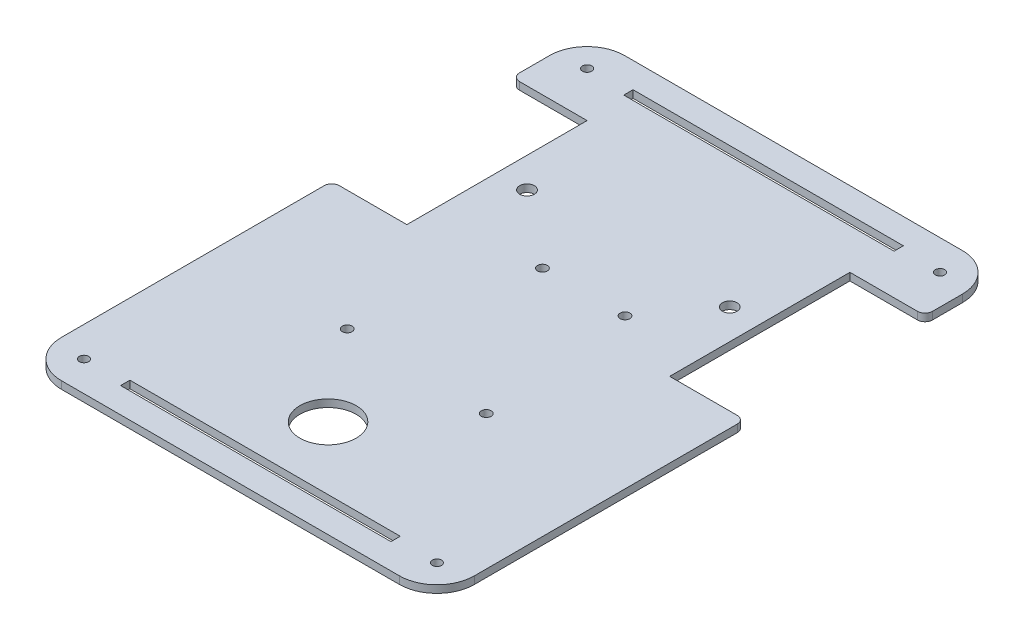
SolidWorks part; units mm, degrees
material "ABS"
ref_plane "Front Plane" through (0, 0, 0) normal (0, 0, 1) x (1, 0, 0)
ref_plane "Top Plane" through (0, 0, 0) normal (0, 1, 0) x (1, 0, 0)
ref_plane "Right Plane" through (0, 0, 0) normal (1, 0, 0) x (0, 0, -1)
sketch "Sketch2" plane through (0, 0, 0) normal (0, 1, 0) x (1, 0, 0)
  line L0 (-148.7583, 0) -> (98.0966, 0) construction
  line L1 (-69.85, -95.25) -> (69.85, -95.25)
  line L2 (-69.85, -95.25) -> (-69.85, 95.25)
  line L3 (-69.85, 95.25) -> (69.85, 95.25)
  line L4 (69.85, -95.25) -> (69.85, 95.25)
  line L5 (-69.85, -95.25) -> (69.85, 95.25) construction
  line L6 (-69.85, 95.25) -> (69.85, -95.25) construction
  line L7 (0, 121.1686) -> (0, -125.6862) construction
  point P0 (0, 0)
  dimension "D1" = 190.5
  dimension "D2" = 139.7
extrude "Base Plate" add sketch "Sketch2" along normal blind 2.54
sketch "Sketch4" plane through (0, 2.54, 0) normal (0, 1, 0) x (1, 0, 0)
  line L0 (0, -95.25) -> (0, 95.25) construction
  line L1 (-69.85, -95.25) -> (69.85, -95.25) construction
  line L2 (69.85, 95.25) -> (-69.85, 95.25) construction
  line L3 (-34.66, -69.85) -> (-34.66, -40.894) construction
  line L4 (-34.66, -40.894) -> (-58.79, -40.894) construction
  line L5 (-58.79, -40.894) -> (-58.79, -69.85) construction
  line L6 (-58.79, -69.85) -> (-34.66, -69.85) construction
  line L7 (69.85, -95.25) -> (69.85, 95.25) construction
  line L8 (-69.85, 95.25) -> (-69.85, -95.25) construction
  circle A0 centre (-58.79, -69.85) radius 1.8415
  circle A1 centre (-34.66, -69.85) radius 1.8415
  circle A2 centre (-34.66, -40.894) radius 1.8415
  circle A3 centre (-58.79, -40.894) radius 1.8415
  circle A4 centre (34.66, -69.85) radius 1.8415
  circle A5 centre (58.79, -69.85) radius 1.8415
  circle A6 centre (58.79, -40.894) radius 1.8415
  circle A7 centre (34.66, -40.894) radius 1.8415
  point P0 (-58.79, -69.85)
  point P1 (-58.79, -40.894)
  point P2 (-34.66, -40.894)
  point P3 (-34.66, -69.85)
  dimension "D4" = 3.683
  dimension "D1" = 28.956
  dimension "D2" = 24.13
  dimension "D3" = 11.06
  dimension "D5" = 25.4
sketch "Sketch5" plane through (0, 2.54, 0) normal (0, 1, 0) x (1, 0, 0)
  line L0 (-69.85, 8.89) -> (-44.45, 8.89)
  line L1 (-69.85, 95.25) -> (-69.85, -95.25) construction
  line L2 (-44.45, 8.89) -> (-44.45, 69.85)
  line L3 (-44.45, 69.85) -> (-69.85, 69.85)
  line L4 (-69.85, 69.85) -> (-69.85, 8.89)
  line L5 (-69.85, -95.25) -> (69.85, -95.25) construction
  line L6 (69.85, 95.25) -> (-69.85, 95.25) construction
  line L7 (0, -95.25) -> (0, 95.25) construction
  line L9 (44.45, 69.85) -> (69.85, 69.85)
  line L10 (44.45, 8.89) -> (44.45, 69.85)
  line L11 (69.85, 8.89) -> (44.45, 8.89)
  line L12 (69.85, 69.85) -> (69.85, 8.89)
  dimension "D1" = 25.4
  dimension "D2" = 60.96
  dimension "D3" = 25.4
extrude "Steering Wheels Holes" cut sketch "Sketch5" against normal blind 6.35
fillet "Fillet1" radius 12.7 4 edges at (69.85, 1.27, -95.25) (-69.85, 1.27, -95.25) (69.85, 1.27, 95.25) (-69.85, 1.27, 95.25)
fillet "Fillet2" radius 2.54 4 edges at (69.85, 1.27, -69.85) (69.85, 1.27, -8.89) (-69.85, 1.27, -8.89) (-69.85, 1.27, -69.85)
sketch "Sketch6" plane through (0, 2.54, 0) normal (0, 1, 0) x (1, 0, 0)
  line L0 (-69.85, -95.25) -> (-69.85, 95.25) construction
  line L1 (-69.85, -95.25) -> (69.85, -95.25) construction
  line L2 (0, -88.935) -> (0, 95.5267) construction
  line L3 (-69.85, 6.35) -> (69.85, 6.35) construction
  point P0 (-59.69, -85.09)
  point P12 (-59.69, 97.79)
  point P13 (59.69, -85.09)
  point P14 (59.69, 97.79)
  point P15 (0, 0)
  dimension "D1" = 10.16
  dimension "D2" = 10.16
sketch "Sketch15" plane through (0, 2.54, 0) normal (0, 1, 0) x (1, 0, 0)
  line L0 (-69.85, -95.25) -> (-69.85, 95.25) construction
  line L1 (-69.85, 95.25) -> (69.85, 95.25) construction
  line L2 (0, 95.25) -> (0, 49.0943) construction
  line L3 (0, 121.1686) -> (0, -125.6862) construction
  point P0 (-59.69, 85.09)
  point P5 (59.69, 85.09)
  dimension "D1" = 10.16
  dimension "D2" = 10.16
sketch "Sketch18" plane through (0, 2.54, 0) normal (0, 1, 0) x (1, 0, 0)
  line L0 (0, 95.25) -> (0, -95.25) construction
  line L1 (57.15, 95.25) -> (-57.15, 95.25) construction
  line L2 (-57.15, -95.25) -> (57.15, -95.25) construction
  line L3 (-24.003, -31.75) -> (78.9561, -31.75) construction
  circle A0 centre (-8.763, 19.05) radius 1.651
  circle A1 centre (19.177, 19.05) radius 1.651
  circle A2 centre (-24.003, -31.75) radius 1.651
  circle A3 centre (24.3097, -33.02) radius 1.651
  point P6 (-8.763, 19.05)
  point P7 (19.177, 19.05)
  point P8 (-24.003, -31.75)
  point P9 (24.257, -26.67)
  dimension "D7" = 3.302
  dimension "D1" = 52.07
  dimension "D2" = 1.27
  dimension "D3" = 5.08
  dimension "D4" = 27.94
  dimension "D5" = 15.24
  dimension "D6" = 50.8
  dimension "D8" = 76.2
extrude "Holes for Arduino UNO" cut sketch "Sketch18" against normal through all
sketch "Sketch20" plane through (0, 2.54, 0) normal (0, 1, 0) x (1, 0, 0)
  line L0 (0, 95.25) -> (0, -95.25) construction
  line L1 (57.15, 95.25) -> (-57.15, 95.25) construction
  line L2 (-57.15, -95.25) -> (57.15, -95.25) construction
  circle A0 centre (0, -62.23) radius 9.525
  dimension "D1" = 19.05
  dimension "D2" = 33.02
extrude "Cutout for motor wires" cut sketch "Sketch20" against normal through all
sketch "Sketch21" plane through (0, 2.54, 0) normal (0, 1, 0) x (1, 0, 0)
  line L0 (-44.45, 39.37) -> (44.45, 39.37) construction
  line L1 (-44.45, 8.89) -> (-44.45, 69.85) construction
  line L2 (44.45, 69.85) -> (44.45, 8.89) construction
  line L3 (0, 95.25) -> (0, -21.3651) construction
  line L4 (57.15, 95.25) -> (-57.15, 95.25) construction
  point P6 (-34.29, 39.37)
  point P12 (34.29, 39.37)
  dimension "D1" = 10.16
hole_wizard "holes for steering " positions "Sketch22" profile "Sketch23" tap size "M6x1.0" standard "ANSI Metric" end condition through all
sketch "Sketch22" plane through (0, 2.54, 0) normal (0, 1, 0) x (1, 0, 0)
  point P0 (-34.29, 39.37)
  point P3 (34.29, 39.37)
sketch "Sketch23" plane through (-34.29, 2.54, -39.37) normal (1, 0, 0) x (0, 0, 1)
  line L0 (0, 0) -> (0, 2.54)
  line L1 (0, 2.54) -> (2.5, 2.54)
  line L2 (2.5, 2.54) -> (2.5, 0)
  line L5 (2.5, 0) -> (0, 0)
  line L11 (0, -6.35) -> (0, 107.95) construction
  dimension "Thru Tap Drill Dia." = 5
  dimension "Thru Tap Drill Depth" = 2.54
cosmetic thread "Hole Thread11" parameters "D2"=6
cosmetic thread "Hole Thread12" parameters "D2"=6
sketch "Sketch24" plane through (0, 2.54, 0) normal (0, 1, 0) x (1, 0, 0)
  line L0 (0, -95.25) -> (0, 95.25) construction
  line L1 (-57.15, -95.25) -> (57.15, -95.25) construction
  line L2 (57.15, 95.25) -> (-57.15, 95.25) construction
  line L3 (-69.85, 82.55) -> (-69.85, 72.39) construction
  circle A0 centre (-59.69, 85.09) radius 1.57
  circle A1 centre (-59.69, 85.09) radius 2.84
  dimension "D1" = 3.14
  dimension "D2" = 10.16
  dimension "D3" = 10.16
  dimension "D4" = 1.27
extrude "Cut-Extrude1" cut sketch "Sketch24" against normal blind 2.54 contours A0 region at (-59.69, 2.54, -85.09)
mirror "Mirror1" about plane through (0, 0, 0) normal (1, 0, 0) of "Cut-Extrude1"
sketch "Sketch25" plane through (0, 2.54, 0) normal (0, 1, 0) x (1, 0, 0)
  line L0 (0, -95.25) -> (0, 95.25) construction
  line L1 (-57.15, -95.25) -> (57.15, -95.25) construction
  line L2 (57.15, 95.25) -> (-57.15, 95.25) construction
  line L3 (-69.85, 6.35) -> (-69.85, -82.55) construction
  circle A0 centre (-59.69, -85.09) radius 1.57
  circle A2 centre (59.69, -85.09) radius 1.57
  dimension "D1" = 3.14
  dimension "D4" = 3.14
  dimension "D2" = 10.16
  dimension "D3" = 10.16
extrude "Cut-Extrude3" cut sketch "Sketch25" against normal blind 2.54
sketch "Sketch27" plane through (0, 2.54, 0) normal (0, 1, 0) x (1, 0, 0)
  line L12 (0, -95.25) -> (0, 166.7066) construction
  line L13 (-57.15, -95.25) -> (57.15, -95.25) construction
  line L14 (-59.69, -87.93) -> (59.69, -87.93) construction
  line L15 (59.69, -82.25) -> (-59.69, -82.25) construction
  line L16 (-45.72, -86.66) -> (45.72, -86.66)
  line L17 (-46.99, -87.93) -> (46.99, -87.93)
  line L18 (-46.99, -87.93) -> (-46.99, -82.25)
  line L19 (-46.99, -82.25) -> (46.99, -82.25)
  line L20 (46.99, -87.93) -> (46.99, -82.25)
  line L21 (45.72, -86.66) -> (45.72, -83.52)
  line L22 (-45.72, -83.52) -> (45.72, -83.52)
  line L23 (-45.72, -86.66) -> (-45.72, -83.52)
  line L24 (-59.69, 82.25) -> (59.69, 82.25) construction
  line L25 (59.69, 87.93) -> (-59.69, 87.93) construction
  line L26 (-45.72, 86.66) -> (45.72, 86.66)
  line L27 (-46.99, 82.25) -> (46.99, 82.25)
  line L28 (-46.99, 82.25) -> (-46.99, 87.93)
  line L29 (-46.99, 87.93) -> (46.99, 87.93)
  line L30 (46.99, 82.25) -> (46.99, 87.93)
  line L31 (45.72, 83.52) -> (45.72, 86.66)
  line L32 (-45.72, 83.52) -> (45.72, 83.52)
  line L33 (-45.72, 83.52) -> (-45.72, 86.66)
  circle A8 centre (-59.69, -85.09) radius 2.84
  circle A9 centre (-59.69, -85.09) radius 1.57 construction
  circle A10 centre (59.69, -85.09) radius 2.84
  circle A11 centre (-59.69, 85.09) radius 2.84
  circle A12 centre (-59.69, 85.09) radius 1.57 construction
  circle A13 centre (59.69, 85.09) radius 2.84
  dimension "D1" = 1.27
  dimension "D5" = 1.27
  dimension "D6" = 12.7
  dimension "D7" = 12.7
  dimension "D2" = 12.7
  dimension "D3" = 12.7
  dimension "D4" = 1.27
  dimension "D8" = 1.27
extrude "Cut-Extrude4" cut sketch "Sketch27" against normal blind 2.54 contours L23 L16 L21 L22 | L26 L31 L32 L33 region at (0, 2.54, 85.09)
